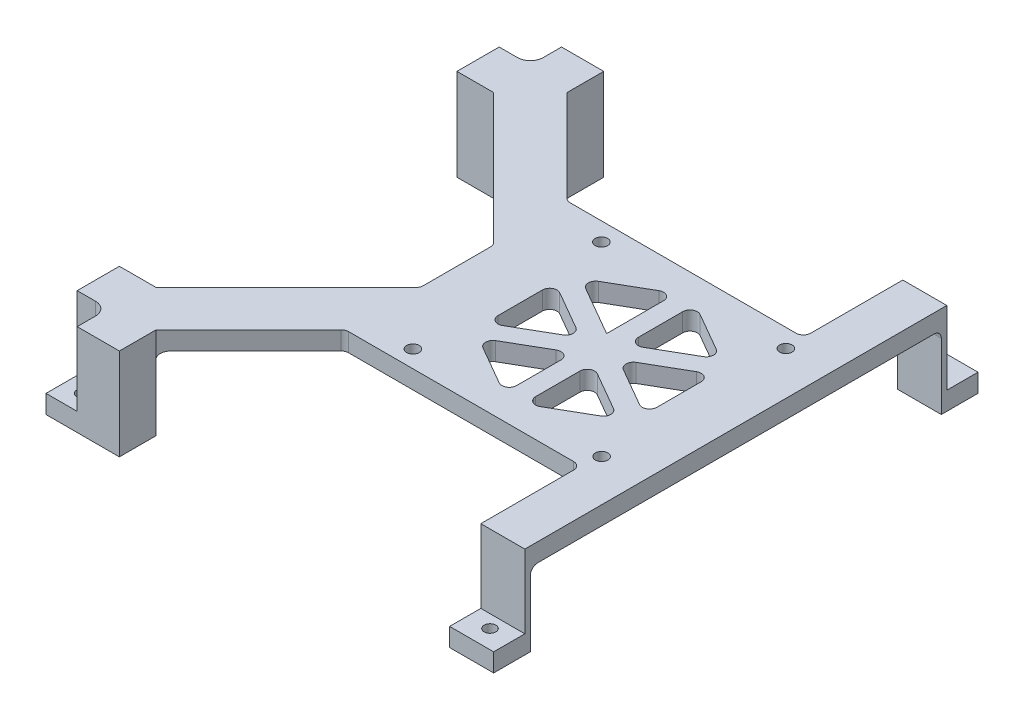
SolidWorks part; units mm, degrees
ref_plane "Plan de face" through (0, 0, 0) normal (0, 0, 1) x (1, 0, 0)
ref_plane "Plan de dessus" through (0, 0, 0) normal (0, 1, 0) x (1, 0, 0)
ref_plane "Plan de droite" through (0, 0, 0) normal (1, 0, 0) x (0, 0, -1)
sketch "Esquisse1" plane through (0, 0, 0) normal (0, 1, 0) x (1, 0, 0)
  line L0 (-55, -46) -> (-65, -46)
  line L1 (-65, -46) -> (-65, -66)
  line L2 (-65, -66) -> (-45, -66)
  line L3 (-45, -66) -> (-45, -56)
  line L5 (-55, -46) -> (-55, -56)
  line L14 (-55, -56) -> (-45, -56)
  line L25 (0, 0) -> (-166.0367, 0) construction
  line L30 (45, -56) -> (57, -56)
  line L31 (45, -56) -> (45, -66)
  line L32 (45, -66) -> (57, -66)
  line L33 (57, -56) -> (57, -66)
  line L34 (-65, 56) -> (-55, 66) construction
  line L35 (45, 66) -> (57, 56) construction
  line L36 (-55, 56) -> (-65, 66) construction
  line L37 (-55, -56) -> (-65, -66) construction
  line L38 (45, -66) -> (57, -56) construction
  line L39 (-65, -56) -> (-55, -66) construction
  line L42 (57, 56) -> (57, 66)
  line L43 (45, 66) -> (57, 66)
  line L44 (45, 56) -> (45, 66)
  line L45 (45, 56) -> (57, 56)
  line L46 (-55, 56) -> (-45, 56)
  line L47 (-55, 46) -> (-55, 56)
  line L48 (-45, 66) -> (-45, 56)
  line L49 (-65, 66) -> (-45, 66)
  line L50 (-65, 46) -> (-65, 66)
  line L51 (-55, 46) -> (-65, 46)
  point P2 (-166.0367, 0)
  point P21 (-60, -61)
  point P32 (51, -61)
  point P39 (51, 61)
  point P40 (-60, 61)
  point P42 (0, 0)
  dimension "D1" = 10
  dimension "D2" = 90
  dimension "D3" = 10
  dimension "D4" = 10
  dimension "D10" = 12
  dimension "D12" = 45
  dimension "D13" = 45
  dimension "D15" = 20
  dimension "D16" = 20
  dimension "D19" = 90
  dimension "D20" = 90
  dimension "D24" = 90
  dimension "D25" = 90
  dimension "D26" = 56
  dimension "D28" = 66
extrude "Boss.-Extru.1" add sketch "Esquisse1" along normal blind 25
ref_plane "Plan1" through (0, 25, 0) normal (0, 1, 0) x (1, 0, 0)
sketch "Esquisse28" plane through (0, 25, 0) normal (0, 1, 0) x (1, 0, 0)
  line L0 (57, -56) -> (45, -56) construction
  line L1 (45, -56) -> (45, -30.192) construction
  line L3 (45, -30.192) -> (-19.192, -30.192) construction
  line L4 (-19.192, -30.192) -> (-45, -56) construction
  line L5 (-45, -56) -> (-55, -56) construction
  line L6 (-55, -56) -> (-55, -46) construction
  line L7 (-55, -46) -> (-19, -10) construction
  line L8 (-19, -10) -> (-19, 10) construction
  line L9 (-19, 10) -> (-55, 46) construction
  line L10 (-55, 46) -> (-55, 56) construction
  line L11 (-55, 56) -> (-45, 56) construction
  line L12 (-45, 56) -> (-19.4093, 30.4093) construction
  line L13 (-19.4093, 30.4093) -> (45, 30.4093) construction
  line L15 (45, 30.4093) -> (45, 56) construction
  line L19 (0, 0) -> (-166.0367, 0) construction
  line L20 (45, 56) -> (57, 56) construction
  line L21 (57, 56) -> (57, -56) construction
  circle A0 centre (45.237, 25.4093) radius 1.705 construction
  circle A1 centre (45.6027, -25.192) radius 1.705 construction
  circle A2 centre (-5.0396, 25.4093) radius 1.705 construction
  circle A3 centre (-5.4704, -25.5275) radius 1.705 construction
  point P2 (-46, 56)
  point P32 (55.9204, -56)
  dimension "D1" = 135
  dimension "D2" = 90
  dimension "D5" = 5
  dimension "D6" = 135
  dimension "D7" = 5
  dimension "D8" = 10
sketch "Esquisse2" plane through (0, 25, 0) normal (0, -1, 0) x (1, 0, 0)
  circle A0 centre (-5.4704, 25.5275) radius 1.705 construction
  circle A1 centre (45.237, -25.4093) radius 1.705 construction
  circle A2 centre (-5.0396, -25.4093) radius 1.705 construction
  circle A3 centre (45.6027, 25.192) radius 1.705 construction
  point P2 (-5.4704, 25.5275)
  point P4 (0, 0)
  point P5 (0, 0)
  point P6 (-5.4053, -19.3244)
  point P17 (-5.0396, -25.4093)
  point P19 (45.237, -25.4093)
  point P21 (45.6027, 25.192)
  point P23 (-5.4704, 25.192)
  point P24 (-5.4704, 25.192)
  point P25 (0, 0)
sketch "Esquisse3" plane through (0, 25, 0) normal (0, 1, 0) x (1, 0, 0)
  line L80 (-19.192, -30.192) -> (-45, -56)
  line L94 (-45, -56) -> (-55, -56)
  line L96 (-55, -56) -> (-55, -46)
  line L99 (-55, -46) -> (-19, -10)
  line L102 (-19, -10) -> (-19, 10)
  line L109 (-19, 10) -> (-55, 46)
  line L110 (-55, 46) -> (-55, 56)
  line L111 (-55, 56) -> (-45, 56)
  line L112 (-45, 56) -> (-19.4093, 30.4093)
  line L113 (-19.4093, 30.4093) -> (45, 30.4093)
  line L114 (45, 30.4093) -> (45, 56)
  line L115 (45, 56) -> (57, 56)
  line L116 (57, 56) -> (57, -56)
  line L117 (57, -56) -> (45, -56)
  line L118 (45, -56) -> (45, -30.192)
  line L119 (45, -30.192) -> (-19.192, -30.192)
  point P16 (-56, 56)
  point P17 (-56, 46)
  point P18 (-46, 56)
  point P19 (-20, 10)
  point P20 (-20, -10)
  point P21 (-20.4093, 30.4093)
  point P22 (44, 30.4093)
  point P23 (44, 56)
  point P24 (56, 56)
  point P25 (56, -56)
  point P26 (44, -56)
  point P27 (44, -30.192)
  point P28 (-20.192, -30.192)
  point P29 (-20, -10)
  point P30 (-56, -46)
  point P31 (-56, -56)
  point P32 (-46, -56)
  point P33 (-56, 56)
  point P34 (0, 0)
extrude "Boss.-Extru.2" add sketch "Esquisse3" against normal blind 5
sketch "Esquisse5" plane through (0, 25, 0) normal (0, -1, 0) x (1, 0, 0)
  line L1 (-65, 66) -> (-56.5, 66)
  line L2 (-65, 66) -> (-45, 66) construction
  line L3 (-56.5, 66) -> (-56.5, 61)
  line L4 (-65, 66) -> (-65, 57.5)
  line L5 (-65, 46) -> (-65, 66) construction
  line L6 (-65, 57.5) -> (-60, 57.5)
  line L7 (-55, 56) -> (-65, 66) construction
  arc A4 (-56.5, 61) -> (-60, 57.5) centre (-60, 61) cw
  dimension "D1" = 5
  dimension "D2" = 5
  dimension "D3" = 8.5
  dimension "D4" = 8.5
  dimension "D5" = 3.5
extrude "Enlèv. mat.-Extru.1" cut sketch "Esquisse5" along normal blind 20
sketch "Esquisse6" plane through (0, 25, 0) normal (0, -1, 0) x (1, 0, 0)
  line L4 (-65, -66) -> (-56.5, -66)
  line L5 (-65, -66) -> (-65, -57.5)
  line L6 (-56.5, -66) -> (-56.5, -61)
  line L7 (-65, -57.5) -> (-60, -57.5)
  line L8 (-55, -56) -> (-65, -66) construction
  arc A3 (-60, -57.5) -> (-56.5, -61) centre (-60, -61) cw
  point P2 (-60, -61.0239)
  point P7 (-59.9934, -59.9934)
  dimension "D1" = 8.5
  dimension "D5" = 3.5
  dimension "D2" = 0
  dimension "D3" = 5
  dimension "D4" = 5
  dimension "D6" = 8.5
sketch "Esquisse7" plane through (0, 25, 0) normal (0, -1, 0) x (1, 0, 0)
  line L0 (57, -66) -> (45, -66)
  line L7 (45, -66) -> (57, -66) construction
  line L9 (57, -66) -> (57, -57.5)
  line L10 (57, -56) -> (57, -66) construction
  line L11 (57, -57.5) -> (45, -57.5)
  line L13 (45, -56) -> (45, -66) construction
  line L14 (45, -66) -> (45, -57.5)
  dimension "D2" = 8.5
sketch "Esquisse8" plane through (0, 25, 0) normal (0, -1, 0) x (1, 0, 0)
  line L1 (57, 56) -> (57, 66) construction
  line L2 (57, 57.5) -> (57, 66)
  line L4 (57, 57.5) -> (45, 57.5)
  line L7 (45, 56) -> (45, 66) construction
  line L8 (45, 57.5) -> (45, 66)
  line L9 (45, 66) -> (57, 66)
  point P2 (0, 0)
  point P8 (0, 0)
  point P9 (55.864, 66)
  dimension "D1" = 12
  dimension "D4" = 8.5
  dimension "D7" = 0
extrude "Enlèv. mat.-Extru.6" cut sketch "Esquisse6" along normal blind 20
extrude "Enlèv. mat.-Extru.7" cut sketch "Esquisse7" along normal blind 20
extrude "Enlèv. mat.-Extru.8" cut sketch "Esquisse8" along normal blind 20
hole_wizard "Dégagement M31" positions "Esquisse11" profile "Esquisse12" hole size "M3" standard "Ansi Metric" end condition through all
sketch "Esquisse11" plane through (0, 20, 0) normal (0, -1, 0) x (-1, 0, 0)
  point P0 (5.0396, 25.4093)
  point P3 (-45.237, 25.4093)
  point P6 (-45.6027, -25.192)
  point P9 (5.4704, -25.5275)
sketch "Esquisse12" plane through (-5.0396, 20, -25.4093) normal (1, 0, 0) x (0, 0, -1)
  line L0 (0, 0) -> (0, 5)
  line L1 (0, 5) -> (1.7, 5)
  line L2 (1.7, 5) -> (1.7, 0)
  line L5 (1.7, 0) -> (0, 0)
  line L11 (0, -6.35) -> (0, 107.95) construction
  dimension "Diamètre du perçage jusqu'au prochain" = 3.4
  dimension "Profondeur du perçage jusqu'au prochain" = 5
hole_wizard "Dégagement M33" positions "Esquisse32" profile "Esquisse33" hole size "M3" standard "Ansi Metric" end condition through all
sketch "Esquisse32" plane through (0, 5, 0) normal (0, 1, 0) x (1, 0, 0)
  point P0 (-60, 61)
  point P3 (51, 61)
  point P6 (51, -61)
  point P9 (-60, -61)
sketch "Esquisse33" plane through (-60, 5, -61) normal (1, 0, 0) x (0, 0, 1)
  line L0 (0, 0) -> (0, 5)
  line L1 (0, 5) -> (1.6, 5)
  line L2 (1.6, 5) -> (1.6, 0)
  line L5 (1.6, 0) -> (0, 0)
  line L11 (0, -6.35) -> (0, 107.95) construction
  dimension "Diamètre du perçage jusqu'au prochain" = 3.2
  dimension "Profondeur du perçage jusqu'au prochain" = 5
sketch "Esquisse26" plane through (0, 20, 0) normal (0, -1, 0) x (-1, 0, 0)
  line L1 (-41.5339, 12.5) -> (-41.5339, -12.5)
  line L2 (-41.5339, -12.5) -> (-19.8833, -25)
  line L3 (-19.8833, -25) -> (1.7673, -12.5)
  line L4 (1.7673, -12.5) -> (1.7673, 12.5)
  line L5 (1.7673, 12.5) -> (-19.8833, 25)
  line L6 (-19.8833, 25) -> (-41.5339, 12.5)
  line L8 (5.0396, 25.4093) -> (-45.6027, -25.192) construction
  line L9 (5.4704, -25.5275) -> (-45.237, 25.4093) construction
  circle A1 centre (-19.8833, 0) radius 21.6506 construction
  point P2 (-19.8833, -0.0591)
  dimension "D1" = 19.8833
  dimension "D2" = 25
  dimension "D3" = 0
extrude "Enlèv. mat.-Extru.5" cut sketch "Esquisse26" against normal up to next
sketch "Esquisse27" plane through (0, 20, 0) normal (0, -1, 0) x (-1, 0, 0)
  line L0 (1.7673, 12.5) -> (-19.8833, 25) construction
  line L1 (-19.8833, -25) -> (1.7673, -12.5) construction
  line L3 (-19.8833, 25) -> (-19.8833, -25) construction
  line L5 (-22.4814, -23.5) -> (-19.8833, -25)
  line L7 (-22.4814, -23.5) -> (-22.4814, -4.5)
  line L8 (-22.4814, 23.5) -> (-22.4814, 4.5)
  line L9 (-41.5339, 9.5) -> (-25.0794, 0)
  line L11 (-38.9359, 14) -> (-22.4814, 4.5)
  line L12 (-22.4814, -4.5) -> (-38.9359, -14)
  line L14 (-41.5339, -9.5) -> (-25.0794, 0)
  line L16 (-19.8833, 25) -> (-22.4814, 23.5)
  line L19 (-38.9359, 14) -> (-41.5339, 12.5)
  line L26 (1.7673, -12.5) -> (-0.8307, -14)
  line L27 (1.7673, -9.5) -> (1.7673, -12.5)
  line L30 (1.7673, 12.5) -> (1.7673, 9.5)
  line L31 (-0.8307, 14) -> (1.7673, 12.5)
  line L32 (-19.8833, 25) -> (-17.2852, 23.5)
  line L33 (1.7673, -9.5) -> (-14.6871, 0)
  line L34 (-17.2852, -4.5) -> (-0.8307, -14)
  line L35 (-0.8307, 14) -> (-17.2852, 4.5)
  line L36 (1.7673, 9.5) -> (-14.6871, 0)
  line L37 (-17.2852, 23.5) -> (-17.2852, 4.5)
  line L38 (-17.2852, -23.5) -> (-17.2852, -4.5)
  line L39 (-17.2852, -23.5) -> (-19.8833, -25)
  line L40 (-19.8833, 25) -> (-41.5339, 12.5) construction
  line L41 (-41.5339, 12.5) -> (-41.5339, -12.5) construction
  line L42 (-41.5339, -12.5) -> (-19.8833, -25) construction
  line L43 (-41.5339, 12.5) -> (-41.5339, 9.5)
  line L44 (-41.5339, -9.5) -> (-41.5339, -12.5)
  line L45 (-41.5339, -12.5) -> (-38.9359, -14)
  dimension "D1" = 60
  dimension "D2" = 3
  dimension "D3" = 60
  dimension "D4" = 3
  dimension "D5" = 3
  dimension "D6" = 3
  dimension "D7" = 3
  dimension "D8" = 60
  dimension "D9" = 3
extrude "Boss.-Extru.5" add sketch "Esquisse27" against normal blind 5
fillet "Congé6" radius 2 27 edges at (17.2852, 22.5, 4.5) (14.6871, 22.5, 0) (0.8307, 22.5, -14) (22.4814, 22.5, -23.5) (38.9359, 22.5, -14) (41.5339, 22.5, -9.5) (41.5339, 22.5, 9.5) (17.2852, 22.5, 23.5) (0.8307, 22.5, 14) (38.9359, 22.5, 14) (22.4814, 22.5, 23.5) (-1.7673, 22.5, -9.5) (45, 22.5, 30.192) (-19.192, 22.5, 30.192) (51, 20, 56) (-50, 20, 56) (-55, 20, 51) (-19, 22.5, -10) (-19, 22.5, 10) (45, 22.5, -30.4093) (-19.4093, 22.5, -30.4093) (25.0794, 22.5, 0) (22.4814, 22.5, -4.5) (-1.7673, 22.5, 9.5) (22.4814, 22.5, 4.5) (17.2852, 22.5, -23.5) (51, 20, -56)
